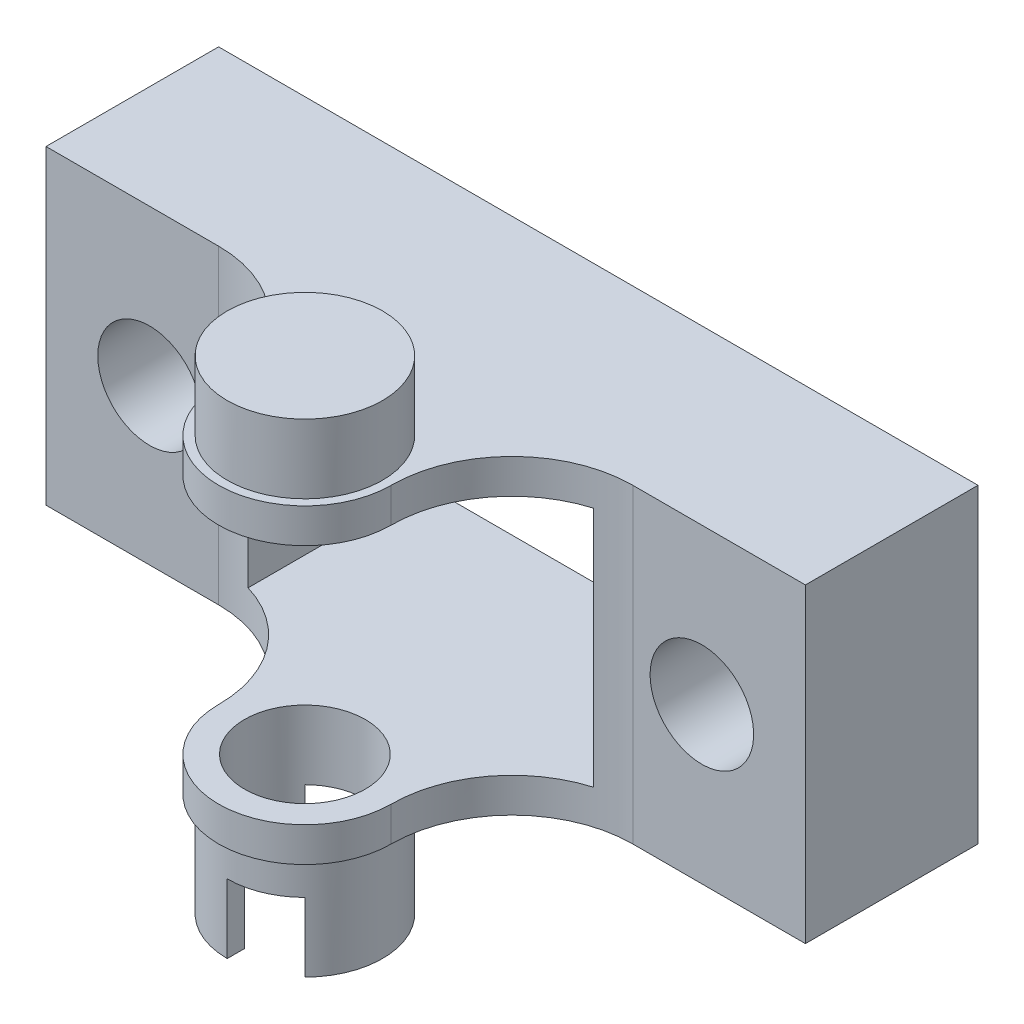
SolidWorks part; units mm, degrees
ref_plane "Front Plane" through (0, 0, 0) normal (0, 0, 1) x (1, 0, 0)
ref_plane "Top Plane" through (0, 0, 0) normal (0, 1, 0) x (1, 0, 0)
ref_plane "Right Plane" through (0, 0, 0) normal (1, 0, 0) x (0, 0, -1)
sketch "Sketch1" plane through (0, 0, 0) normal (0, 0, 1) x (1, 0, 0)
  line L1 (0, 0) -> (420, 0)
  line L2 (0, 0) -> (0, 350)
  line L3 (0, 350) -> (420, 350)
  line L4 (420, 0) -> (420, 350)
  dimension "D1" = 350
  dimension "D2" = 420
extrude "Boss-Extrude1" add sketch "Sketch1" along normal blind 10
sketch "Sketch3" plane through (0, 0, 10) normal (0, 0, 1) x (1, 0, 0)
  line L0 (0, 350) -> (0, 0) construction
  line L1 (30, 340) -> (42, 340)
  line L2 (30, 340) -> (30, 331)
  line L3 (30, 331) -> (42, 331)
  line L4 (42, 340) -> (42, 331)
  line L5 (420, 350) -> (0, 350) construction
  dimension "D1" = 30
  dimension "D2" = 10
  dimension "D3" = 12
  dimension "D4" = 9
fillet "Fillet2" radius 5 4 edges at (420, 0, 5) (420, 350, 5) (0, 350, 5) (0, 0, 5)
extrude "Boss-Extrude2" add sketch "Sketch3" along normal blind 7
sketch "Sketch7" plane through (0, 340, 0) normal (0, 1, 0) x (1, 0, 0)
  line L0 (30, -17) -> (30, -10) construction
  line L1 (415, -10) -> (5, -10) construction
  line L3 (42, -17) -> (42, -10) construction
  circle A0 centre (36, -14.5) radius 2.5
  circle A1 centre (36, -14.5) radius 2.25
  circle A2 centre (36, -14.5) radius 1.75
  circle A3 centre (42, -14.5) radius 3.5
  circle A4 centre (30, -14.5) radius 3.5
  line M2 (30, -10) -> (30, -17)
  line M3 (30, -17) -> (42, -17)
  line M4 (42, -17) -> (42, -10)
  dimension "D3" = 5
  dimension "D4" = 4.5
  dimension "D5" = 3.5
  dimension "D6" = 7
  dimension "D8" = 7
  dimension "D7" = 4.5
  dimension "D9" = 4.5
  dimension "D1" = 6
  dimension "D2" = 4.5
sketch "Sketch8" plane through (0, 0, 17) normal (0, 0, 1) x (1, 0, 0)
  line L0 (30, 340) -> (30, 331) construction
  line L1 (31, 339) -> (41, 339)
  line L2 (31, 339) -> (31, 332)
  line L3 (31, 332) -> (41, 332)
  line L4 (41, 339) -> (41, 332)
  line L5 (33.5, 340) -> (26.5, 340) construction
  line L6 (42, 331) -> (42, 340) construction
  line L7 (30, 331) -> (42, 331) construction
  dimension "D1" = 1
  dimension "D2" = 1
  dimension "D3" = 1
  dimension "D4" = 1
extrude "Cut-Extrude4" cut sketch "Sketch8" against normal blind 7
extrude "Cut-Extrude5" cut sketch "Sketch7" against normal through all contours A4 M3 M2 | A4 A0 M3 | A2 | A3 A0 M3 | A3 M4 M3 region at (38.2679, 340, 16.4241) region at (40.4621, 340, 14.221) region at (31.5379, 340, 14.221) region at (33.7321, 340, 16.4241) region at (36, 340, 14.5)
sketch "Sketch9" plane through (0, 340, 0) normal (0, 1, 0) x (1, 0, 0)
  circle A0 centre (36, -14.5) radius 2.25
  dimension "D1" = 4.5
extrude "Boss-Extrude3" add sketch "Sketch9" along normal blind 3
sketch "Sketch11" plane through (0, 340, 0) normal (0, -1, 0) x (1, 0, 0)
  circle A0 centre (36, 14.5) radius 1.75
  dimension "D1" = 3.5
extrude "Cut-Extrude6" cut sketch "Sketch11" against normal blind 2
sketch "Sketch12" plane through (0, 331, 0) normal (0, -1, 0) x (1, 0, 0)
  circle A0 centre (36, 14.5) radius 2.25
  dimension "D1" = 4.5
extrude "Boss-Extrude4" add sketch "Sketch12" along normal blind 3
sketch "Sketch13" plane through (0, 328, 0) normal (0, -1, 0) x (1, 0, 0)
  circle A0 centre (36, 14.5) radius 1.75
  dimension "D1" = 3.5
extrude "Cut-Extrude7" cut sketch "Sketch13" against normal blind 3
sketch "Sketch14" plane through (0, 328, 0) normal (0, -1, 0) x (1, 0, 0)
  line L0 (36, 14.5) -> (36, 16.75)
  line L1 (36, 14.5) -> (37.591, 16.091)
  line L2 (36, 14.5) -> (36, 12.25)
  line L3 (36, 14.5) -> (34.409, 12.909)
  circle A0 centre (36, 14.5) radius 2.25 construction
  circle A1 centre (36, 14.5) radius 2.25 construction
  circle M5 centre (36, 14.5) radius 1.75
  circle M6 centre (36, 14.5) radius 2.25
  dimension "D1" = 45
  dimension "D2" = 45
extrude "Cut-Extrude8" cut sketch "Sketch14" against normal blind 2 contours L1 L0 M5 M6 | L3 L2 M5 M6 region at (36.7497, 328, 16.31) region at (35.2503, 328, 12.69)
sketch "Sketch17" plane through (0, 343, 0) normal (0, 1, 0) x (1, 0, 0)
  circle A0 centre (36, -14.5) radius 1.75
extrude "Boss-Extrude5" add sketch "Sketch17" against normal blind 1
sketch "Sketch21" plane through (0, 343, 0) normal (0, 1, 0) x (1, 0, 0)
  circle A0 centre (36, -14.5) radius 2.25
extrude "Cut-Extrude12" cut sketch "Sketch21" against normal blind 1
sketch "Sketch22" plane through (0, 342, 0) normal (0, 1, 0) x (1, 0, 0)
  circle A0 centre (36, -14.5) radius 1.75
extrude "Boss-Extrude7" add sketch "Sketch22" against normal blind 1
sketch "Sketch29" plane through (0, 0, 0) normal (0, 0, -1) x (-1, 0, 0)
  line L0 (-420, 5) -> (-420, 345) construction
  line L1 (10, -10) -> (-430, -10)
  line L2 (10, -10) -> (10, 360)
  line L3 (10, 360) -> (-430, 360)
  line L4 (-430, -10) -> (-430, 360)
  line L5 (-415, 350) -> (-5, 350) construction
  line L6 (0, 345) -> (0, 5) construction
  line L7 (-5, 0) -> (-415, 0) construction
  dimension "D1" = 10
  dimension "D2" = 10
  dimension "D3" = 10
  dimension "D4" = 10
extrude "Boss-Extrude11" add sketch "Sketch29" against normal blind 10
fillet "Fillet4" radius 10 4 edges at (-10, 360, 5) (-10, -10, 5) (430, -10, 5) (430, 360, 5)
sketch "Sketch30" plane through (0, 0, 0) normal (0, 0, -1) x (-1, 0, 0)
  line L1 (-469.0893, 407.0539) -> (71.6188, 407.0539)
  line L2 (-469.0893, 407.0539) -> (-469.0893, -72.374)
  line L3 (-469.0893, -72.374) -> (71.6188, -72.374)
  line L4 (71.6188, 407.0539) -> (71.6188, -72.374)
extrude "Cut-Extrude13" cut sketch "Sketch30" against normal blind 10
sketch "Sketch31" plane through (0, 0, 10) normal (0, 0, -1) x (-1, 0, 0)
  line L1 (-42, 340) -> (-30, 340)
  line L2 (-42, 340) -> (-42, 331)
  line L3 (-42, 331) -> (-30, 331)
  line L4 (-30, 340) -> (-30, 331)
  line L5 (-41, 339) -> (-31, 339)
  line L6 (-41, 339) -> (-41, 332)
  line L7 (-41, 332) -> (-31, 332)
  line L8 (-31, 339) -> (-31, 332)
extrude "Boss-Extrude12" add sketch "Sketch31" along normal blind 4
sketch "Sketch32" plane through (30, 0, 0) normal (-1, 0, 0) x (0, 0, 1)
  line L1 (6, 340) -> (11, 340)
  line L2 (6, 340) -> (6, 331)
  line L3 (6, 331) -> (11, 331)
  line L4 (11, 340) -> (11, 331)
extrude "Boss-Extrude13" add sketch "Sketch32" along normal blind 5
sketch "Sketch33" plane through (42, 0, 0) normal (1, 0, 0) x (0, 0, -1)
  line L1 (-11, 340) -> (-6, 340)
  line L2 (-11, 340) -> (-11, 331)
  line L3 (-11, 331) -> (-6, 331)
  line L4 (-6, 340) -> (-6, 331)
extrude "Boss-Extrude14" add sketch "Sketch33" along normal blind 5
sketch "Sketch34" plane through (0, 0, 6) normal (0, 0, -1) x (-1, 0, 0)
  line L0 (-25, 340) -> (-47, 340) construction
  line L3 (-25, 340) -> (-25, 331) construction
  line L4 (-41, 339) -> (-41, 332) construction
  circle A0 centre (-28, 335.5) radius 1.5
  circle A1 centre (-44, 335.5) radius 1.5
  dimension "D1" = 3
  dimension "D2" = 3
  dimension "D3" = 4.5
  dimension "D4" = 4.5
  dimension "D5" = 3
  dimension "D6" = 3
extrude "Cut-Extrude14" cut sketch "Sketch34" against normal blind 5
sketch "Sketch35" plane through (0, 0, 6) normal (0, 0, -1) x (-1, 0, 0)
  line L0 (-25, 340) -> (-47, 340) construction
  circle A0 centre (-44, 335.5) radius 1.5 construction
